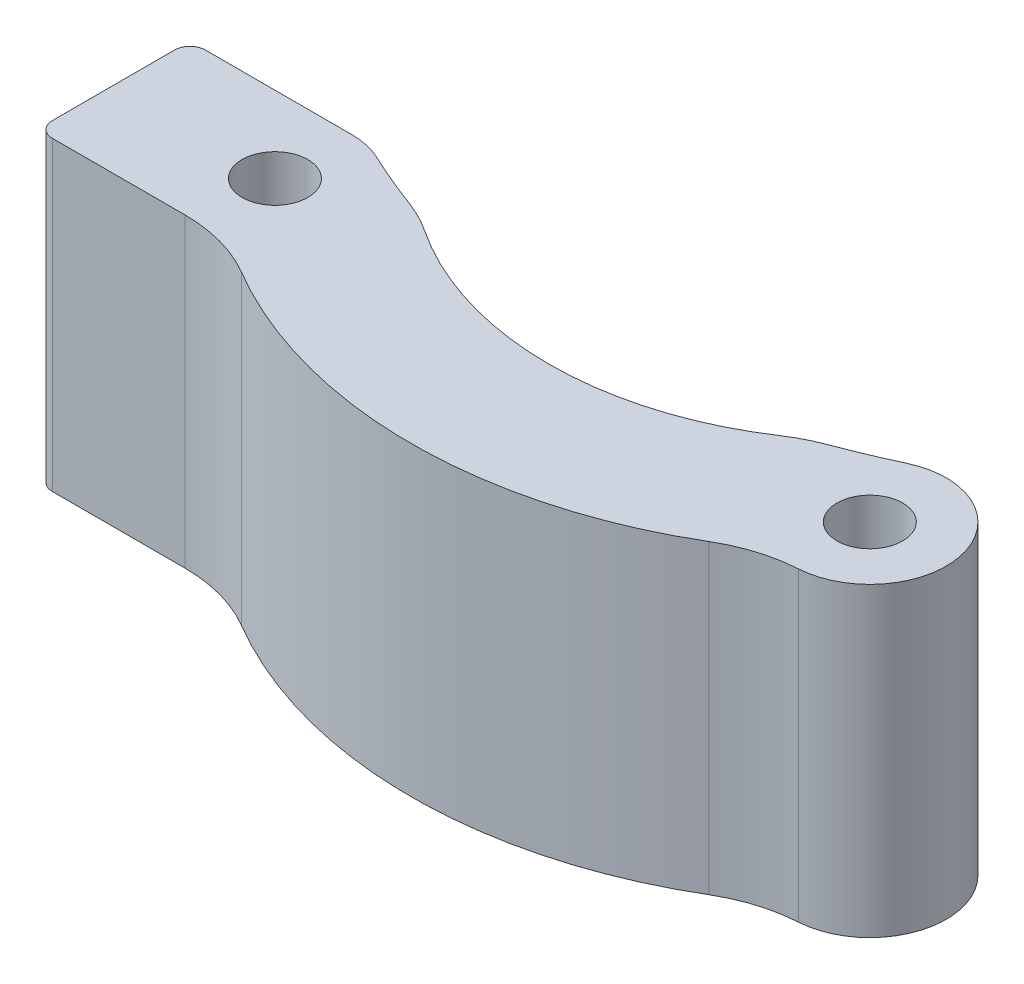
SolidWorks part; units mm, degrees
material "3DP"
ref_plane "正面" through (0, 0, 0) normal (0, 0, 1) x (1, 0, 0)
ref_plane "平面" through (0, 0, 0) normal (0, 1, 0) x (1, 0, 0)
ref_plane "右側面" through (0, 0, 0) normal (1, 0, 0) x (0, 0, -1)
sketch "ｽｹｯﾁ1" plane through (0, 0, 0) normal (0, 1, 0) x (1, 0, 0)
  line L0 (0, 0) -> (-19.4454, -19.4454) construction
  line L1 (0, 0) -> (27.5, 0) construction
  line L2 (0, 0) -> (0, 21) construction
  line L3 (-30, 45.3128) -> (-30, -10.7981) construction
  line L4 (-30, -24.4454) -> (-19.4454, -24.4454)
  line L5 (-14.8492, -14.8492) -> (-15.9099, -15.9099)
  line L6 (14.8492, -14.8492) -> (15.9099, -15.9099)
  line L7 (-19.4454, -14.4454) -> (-30, -14.4454)
  line L8 (-30, -14.4454) -> (-30, -24.4454)
  line L9 (17.3902, -24.4454) -> (19.4454, -24.4454) construction
  line L10 (12.5965, -24.4454) -> (17.3902, -24.4454) construction
  line L11 (-12.5965, -24.4454) -> (12.5965, -24.4454) construction
  line L12 (-19.4454, -24.4454) -> (-17.3902, -24.4454) construction
  line L13 (-17.3902, -24.4454) -> (-12.5965, -24.4454) construction
  arc A0 (-14.8492, -14.8492) -> (14.8492, -14.8492) centre (0, 0) ccw
  circle A1 centre (0, 0) radius 27.5 construction
  arc A3 (-19.4454, -24.4454) -> (-17.7832, -24.1611) centre (-19.4454, -19.4454) ccw
  circle A4 centre (-19.4454, -19.4454) radius 2.15
  circle A5 centre (19.4454, -19.4454) radius 2.15
  arc A6 (15.9099, -15.9099) -> (17.7832, -24.1611) centre (19.4454, -19.4454) cw
  arc A7 (-17.7832, -24.1611) -> (17.7832, -24.1611) centre (0, 0) ccw
  arc A9 (-24.1611, -17.7832) -> (-17.7832, -24.1611) centre (0, 0) ccw construction
  arc A10 (-30, 0) -> (-24.1611, -17.7832) centre (0, 0) ccw construction
  arc A11 (24.1611, -17.7832) -> (-30, 0) centre (0, 0) ccw construction
  arc A12 (17.7832, -24.1611) -> (24.1611, -17.7832) centre (0, 0) ccw construction
  arc A13 (0, 21) -> (-14.8492, -14.8492) centre (0, 0) ccw construction
  arc A14 (21, 0) -> (0, 21) centre (0, 0) ccw construction
  arc A15 (14.8492, -14.8492) -> (21, 0) centre (0, 0) ccw construction
  arc A16 (-19.4454, -14.4454) -> (-22.6449, -15.6031) centre (-19.4454, -19.4454) ccw construction
  arc A17 (-22.6449, -15.6031) -> (-24.1611, -17.7832) centre (-19.4454, -19.4454) ccw construction
  arc A18 (-24.1611, -17.7832) -> (-19.4454, -24.4454) centre (-19.4454, -19.4454) ccw construction
  arc A19 (-17.7832, -24.1611) -> (-15.6031, -22.6449) centre (-19.4454, -19.4454) ccw construction
  arc A20 (-15.9099, -15.9099) -> (-19.4454, -14.4454) centre (-19.4454, -19.4454) ccw
  arc A21 (-15.6031, -22.6449) -> (-15.9099, -15.9099) centre (-19.4454, -19.4454) ccw construction
  arc A22 (15.6031, -22.6449) -> (15.9099, -15.9099) centre (19.4454, -19.4454) cw construction
  arc A23 (17.7832, -24.1611) -> (15.6031, -22.6449) centre (19.4454, -19.4454) cw construction
  dimension "D1" = 42
  dimension "D2" = 55
  dimension "D3" = 135
  dimension "D4" = 10
  dimension "D5" = 4.3
  dimension "D6" = 60
extrude "ﾎﾞｽ - 押し出し1" add sketch "ｽｹｯﾁ1" along normal blind 20
fillet "ﾌｨﾚｯﾄ1" radius 10 4 edges at (17.7832, 10, 24.1611) (-17.7832, 10, 24.1611) (-14.8492, 10, 14.8492) (14.8492, 10, 14.8492)
fillet "ﾌｨﾚｯﾄ2" radius 50 2 edges at (-15.9099, 10, 15.9099) (15.9099, 10, 15.9099)
fillet "ﾌｨﾚｯﾄ3" radius 1 2 edges at (-30, 10, 24.4454) (-30, 10, 14.4454)
